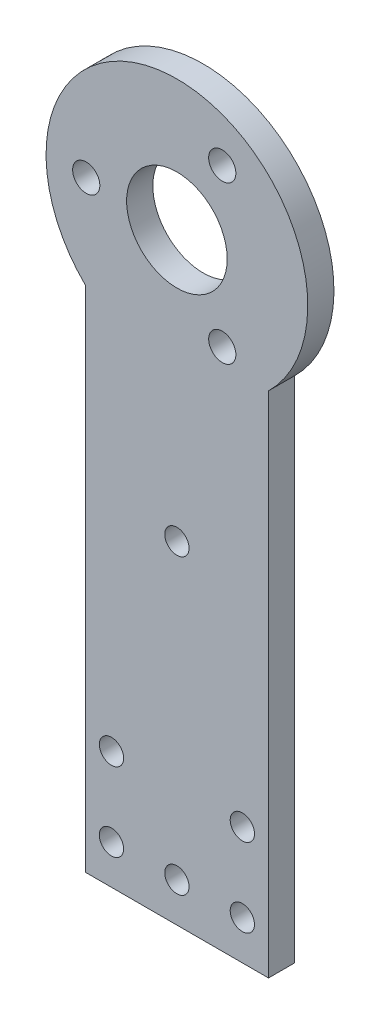
SolidWorks part; units mm, degrees
material "6061-T6 (SS)"
ref_plane "Front Plane" through (0, 0, 0) normal (0, 0, 1) x (1, 0, 0)
ref_plane "Top Plane" through (0, 0, 0) normal (0, 1, 0) x (1, 0, 0)
ref_plane "Right Plane" through (0, 0, 0) normal (1, 0, 0) x (0, 0, -1)
sketch "Sketch1" plane through (0, 0, 0) normal (0, 0, 1) x (1, 0, 0)
  line L0 (-11.1125, -11.337) -> (-11.1125, -73.025)
  line L1 (11.1125, -11.337) -> (11.1125, -73.025)
  line L2 (11.1125, -73.025) -> (-11.1125, -73.025)
  line L3 (0, 0) -> (0, -73.025) construction
  arc A0 (11.1125, -11.337) -> (-11.1125, -11.337) centre (0, 0) ccw
  circle A1 centre (-11, 0) radius 1.65
  circle A2 centre (5.5, 9.5263) radius 1.65
  circle A3 centre (5.5, -9.5263) radius 1.65
  circle A4 centre (0, 0) radius 6.1
  point P10 (0, 11)
  point P11 (0, 0)
  point P15 (0, 0)
  point P17 (-11.1125, 0.2573)
  point P18 (0, 0)
  dimension "D1" = 22.225
  dimension "D4" = 15.875
  dimension "D5" = 3.3
  dimension "D7" = 12.2
  dimension "D2" = 73.025
  dimension "D3" = 11
  dimension "D6" = 3
extrude "Boss-Extrude1" add sketch "Sketch1" along normal blind 3.175
hole_wizard "#4 Clearance Hole2" positions "Sketch2" profile "Sketch3" hole size "#4" standard "ANSI Inch"
sketch "Sketch2" plane through (0, 0, 0) normal (0, 0, -1) x (-1, 0, 0)
  line L0 (0, -73.025) -> (0, -65.4664) construction
  line L1 (11.1125, -73.025) -> (-11.1125, -73.025) construction
  point P0 (7.9375, -68.2625)
  point P2 (-7.9375, -68.2625)
  point P4 (-7.9375, -58.7375)
  point P6 (7.9375, -58.7375)
  dimension "D1" = 15.875
  dimension "D2" = 9.525
  dimension "D3" = 4.7625
sketch "Sketch3" plane through (-7.9375, -68.2625, 0) normal (1, 0, 0) x (0, 1, 0)
  line L0 (0, 0) -> (0, 10.7912)
  line L1 (0, 10.7912) -> (1.4732, 9.906)
  line L2 (1.4732, 9.906) -> (1.4732, 0)
  line L5 (1.4732, 0) -> (0, 0)
  line L10 (0, 10.7912) -> (-1.4732, 9.906) construction
  line L11 (0, -6.35) -> (0, 107.95) construction
  dimension "Hole Dia." = 2.9464
  dimension "Hole Depth" = 9.906
  dimension "Drill Angle" = 118
sketch "Sketch4" plane through (0, 0, 0) normal (0, 0, -1) x (-1, 0, 0)
  line L0 (0, -73.025) -> (0, -47.1239) construction
  line L1 (11.1125, -73.025) -> (-11.1125, -73.025) construction
  line L3 (-2.5, -68.525) -> (2.5, -68.525)
  line L4 (-2.5, -68.525) -> (-2.5, -53.525)
  line L5 (-2.5, -53.525) -> (2.5, -53.525)
  line L6 (2.5, -68.525) -> (2.5, -53.525)
  line L7 (-2.5, -68.525) -> (2.5, -53.525) construction
  line L8 (-2.5, -53.525) -> (2.5, -68.525) construction
  point P5 (0, -61.025)
  dimension "D1" = 15
  dimension "D2" = 5
  dimension "D3" = 12
extrude "SERVO-SLOT" [suppressed] cut sketch "Sketch4" against normal up to next
fillet "TOOLING-RADIUS" [suppressed] radius 1.5875
hole_wizard "#4 Clearance Hole1" positions "Sketch5" profile "Sketch6" hole size "#4" standard "ANSI Inch" end condition up to next
sketch "Sketch5" plane through (0, 0, 0) normal (0, 0, -1) x (-1, 0, 0)
  line L0 (11.1125, -73.025) -> (-11.1125, -73.025) construction
  point P0 (0, -68.2625)
  point P2 (0, -32.7025)
  dimension "D1" = 35.56
  dimension "D2" = 4.7625
sketch "Sketch6" plane through (0, -68.2625, 0) normal (1, 0, 0) x (0, 1, 0)
  line L0 (0, 0) -> (0, 3.175)
  line L1 (0, 3.175) -> (1.4732, 3.175)
  line L2 (1.4732, 3.175) -> (1.4732, 0)
  line L5 (1.4732, 0) -> (0, 0)
  line L11 (0, -6.35) -> (0, 107.95) construction
  dimension "Thru Hole Dia." = 2.9464
  dimension "Thru Hole Depth" = 3.175
